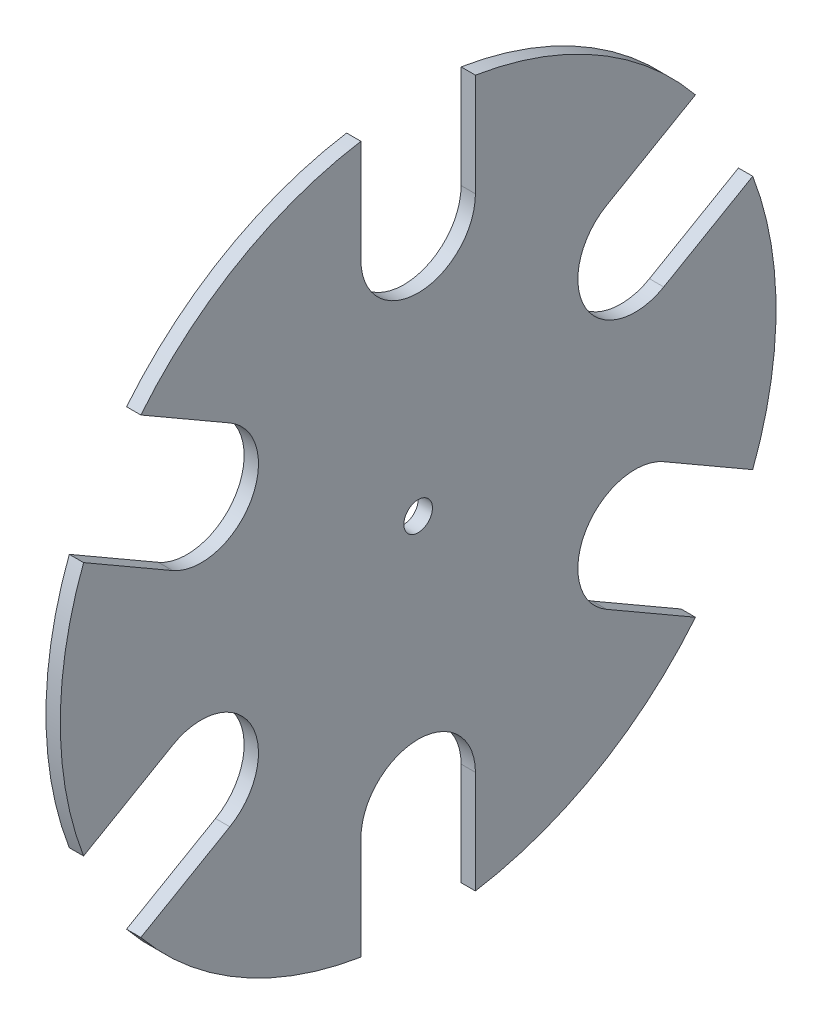
SolidWorks part; units mm, degrees
material "AISI 304"
ref_plane "Front Plane" through (0, 0, 0) normal (0, 0, 1) x (1, 0, 0)
ref_plane "Top Plane" through (0, 0, 0) normal (0, 1, 0) x (1, 0, 0)
ref_plane "Right Plane" through (0, 0, 0) normal (1, 0, 0) x (0, 0, -1)
sketch "Sketch1" plane through (0, 0, 0) normal (1, 0, 0) x (0, 0, -1)
  line L0 (0, 0) -> (0, 250) construction
  line L1 (0, 0) -> (216.5064, 125) construction
  line L2 (0, 0) -> (216.5064, -125) construction
  line L3 (0, 0) -> (0, -250) construction
  line L4 (0, 0) -> (-216.5064, -125) construction
  line L5 (0, 0) -> (-216.5064, 125) construction
  circle A0 centre (0, 0) radius 250
  circle A1 centre (0, 0) radius 10
  circle A2 centre (0, 175) radius 40
  circle A3 centre (151.5544, 87.5) radius 40
  circle A4 centre (151.5544, -87.5) radius 40
  circle A5 centre (0, -175) radius 40
  circle A6 centre (-151.5544, -87.5) radius 40
  circle A7 centre (-151.5544, 87.5) radius 40
  point P13 (0, 0)
  point P26 (0, 0)
  dimension "D1" = 500
  dimension "D2" = 20
  dimension "D4" = 80
  dimension "D5" = 175
  dimension "D3" = 6
  dimension "D6" = 6
extrude "Boss-Extrude1" add sketch "Sketch1" along normal blind 10
ref_plane "Plane1" through (10, 0, 0) normal (-1, 0, 0) x (0, 0, 1)
sketch "Sketch2" plane through (0, 0, 0) normal (-1, 0, 0) x (0, 0, 1)
  line L0 (-40, 175) -> (-40, 246.7793)
  line L1 (40, 175) -> (40, 246.7793)
  line L2 (131.5544, 122.141) -> (193.7171, 158.0306)
  line L3 (171.5544, 52.859) -> (233.7171, 88.7486)
  line L4 (171.5544, -52.859) -> (233.7171, -88.7486)
  line L5 (131.5544, -122.141) -> (193.7171, -158.0306)
  line L6 (40, -175) -> (40, -246.7793)
  line L7 (-40, -175) -> (-40, -246.7793)
  line L8 (-131.5544, -122.141) -> (-193.7171, -158.0306)
  line L9 (-171.5544, -52.859) -> (-233.7171, -88.7486)
  line L10 (-171.5544, 52.859) -> (-233.7171, 88.7486)
  line L11 (-131.5544, 122.141) -> (-193.7171, 158.0306)
  circle A0 centre (0, 175) radius 40 construction
  circle A1 centre (0, 0) radius 250 construction
  arc A2 (-40, 175) -> (40, 175) centre (0, 175) cw
  arc A3 (-40, 246.7793) -> (40, 246.7793) centre (0, 0) cw
  arc A4 (131.5544, 122.141) -> (171.5544, 52.859) centre (151.5544, 87.5) cw
  arc A5 (193.7171, 158.0306) -> (233.7171, 88.7486) centre (0, 0) cw
  arc A6 (171.5544, -52.859) -> (131.5544, -122.141) centre (151.5544, -87.5) cw
  arc A7 (233.7171, -88.7486) -> (193.7171, -158.0306) centre (0, 0) cw
  arc A8 (40, -175) -> (-40, -175) centre (0, -175) cw
  arc A9 (40, -246.7793) -> (-40, -246.7793) centre (0, 0) cw
  arc A10 (-131.5544, -122.141) -> (-171.5544, -52.859) centre (-151.5544, -87.5) cw
  arc A11 (-193.7171, -158.0306) -> (-233.7171, -88.7486) centre (0, 0) cw
  arc A12 (-171.5544, 52.859) -> (-131.5544, 122.141) centre (-151.5544, 87.5) cw
  arc A13 (-233.7171, 88.7486) -> (-193.7171, 158.0306) centre (0, 0) cw
  point P52 (0, 0)
  dimension "D1" = 6
extrude "Cut-Extrude1" cut sketch "Sketch2" against normal through all both and the other way through all
